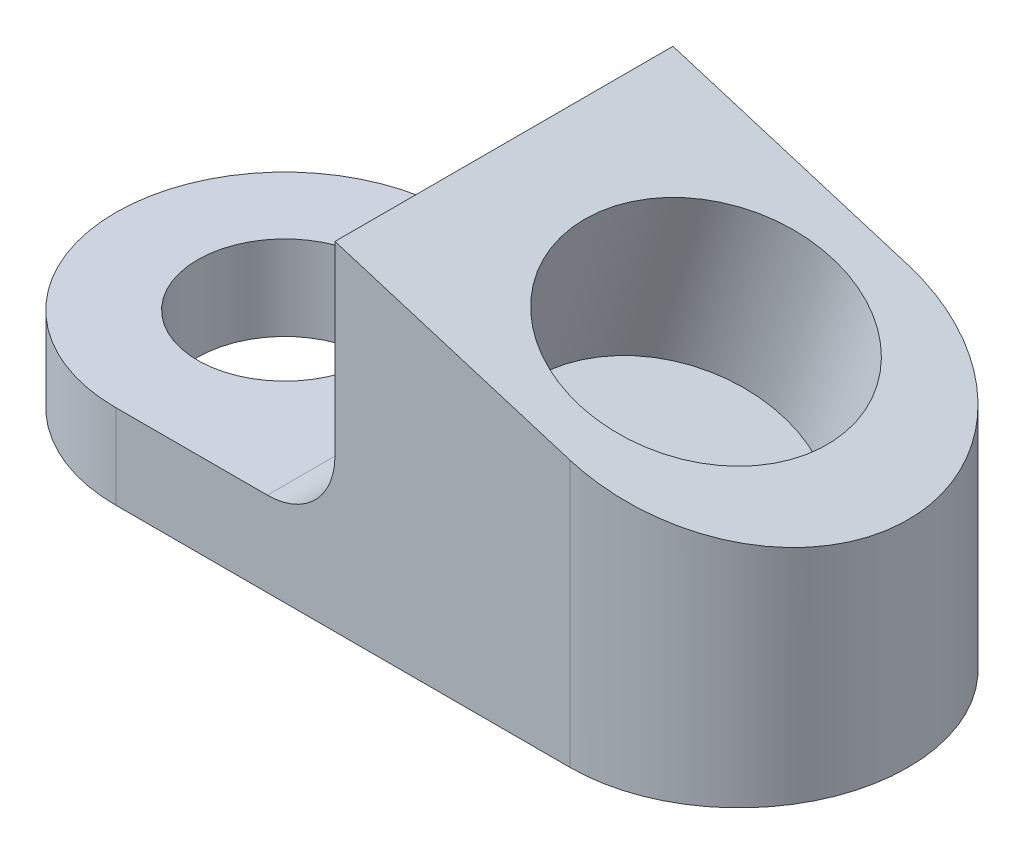
SolidWorks part; units mm, degrees
ref_plane "Front" through (0, 0, 0) normal (0, 0, 1) x (1, 0, 0)
ref_plane "Top" through (0, 0, 0) normal (0, 1, 0) x (1, 0, 0)
ref_plane "Right" through (0, 0, 0) normal (1, 0, 0) x (0, 0, -1)
sketch "Sketch1" plane through (0, 0, 0) normal (0, 0, 1) x (1, 0, 0)
  line L0 (0, 0) -> (63.3062, 0)
  line L1 (63.3062, 0) -> (63.3062, 16.1172)
  line L2 (63.3062, 16.1172) -> (32.9436, 25.4)
  line L3 (32.9436, 25.4) -> (32.9436, 6.35)
  line L4 (32.9436, 6.35) -> (0, 6.35)
  line L5 (0, 6.35) -> (0, 0)
  line L6 (16.4718, 6.35) -> (16.4718, 0) construction
  line L7 (48.1249, 20.7586) -> (41.7784, 0) construction
  point P11 (44.4118, 8.6135)
  dimension "D1" = 31.75
  dimension "D2" = 17
  dimension "D3" = 27.94
  dimension "D4" = 25.4
  dimension "D5" = 6.35
  dimension "D6" = 12.7
extrude "Boss-Extrude1" add sketch "Sketch1" along normal mid plane 25.4
sketch "Sketch2" plane through (9.9178, 32.4397, 0) normal (0.2924, 0.9563, 0) x (0.9563, -0.2924, 0)
  line L0 (24.0778, 0) -> (55.8278, 0) construction
  line L1 (24.0778, -12.7) -> (24.0778, 12.7) construction
  line L2 (55.8278, -12.7) -> (55.8278, 12.7) construction
  line L3 (39.9528, 12.7) -> (39.9528, -12.7) construction
  line L4 (55.8278, 12.7) -> (24.0778, 12.7) construction
  line L5 (55.8278, -12.7) -> (24.0778, -12.7) construction
  circle A0 centre (39.9528, 0) radius 9.525
  dimension "D1" = 19.05
extrude "Cut-Extrude1" cut sketch "Sketch2" against normal blind 12.7
sketch "Sketch3" plane through (0, 6.35, 0) normal (0, 1, 0) x (1, 0, 0)
  line L0 (0, 0) -> (32.9436, 0) construction
  line L1 (32.9436, -12.7) -> (32.9436, 12.7) construction
  circle A0 centre (16.4718, 0) radius 6.5484
  dimension "D1" = 13.0969
extrude "Cut-Extrude2" cut sketch "Sketch3" against normal through all
fillet "Fillet3" 2 edges at (63.3062, 8.0586, 12.7) (63.3062, 8.0586, -12.7) type full round first side face at (32.0833, 9.0362, 12.7) second side face at (32.0833, 9.0362, -12.7) middle face at (63.3062, 8.0586, 0)
sketch "Sketch4" plane through (0, 6.35, 0) normal (0, 1, 0) x (1, 0, 0)
  line L0 (32.9436, 12.7) -> (0, 12.7) construction
  line L5 (32.9436, 12.7) -> (0, 12.7)
  line L6 (0, 12.7) -> (0, -12.7)
  line L7 (0, -12.7) -> (32.9436, -12.7)
  line L8 (32.9436, -12.7) -> (32.9436, 12.7)
  line L9 (16.4718, 12.7) -> (0, 12.7)
  line L10 (0, 12.7) -> (0, -12.7)
  line L11 (0, -12.7) -> (16.4718, -12.7)
  arc A0 (16.4718, 12.7) -> (16.4718, -12.7) centre (16.4718, 0) ccw
  dimension "D1" = 0
extrude "Cut-Extrude3" cut sketch "Sketch4" against normal through all
fillet "Fillet4" radius 5.08 1 edges at (32.9436, 6.35, 0)
sketch "Sketch5" plane through (6.2047, 20.2946, 0) normal (0.2924, 0.9563, 0) x (0.9563, -0.2924, 0)
  point P0 (39.9528, 0)
